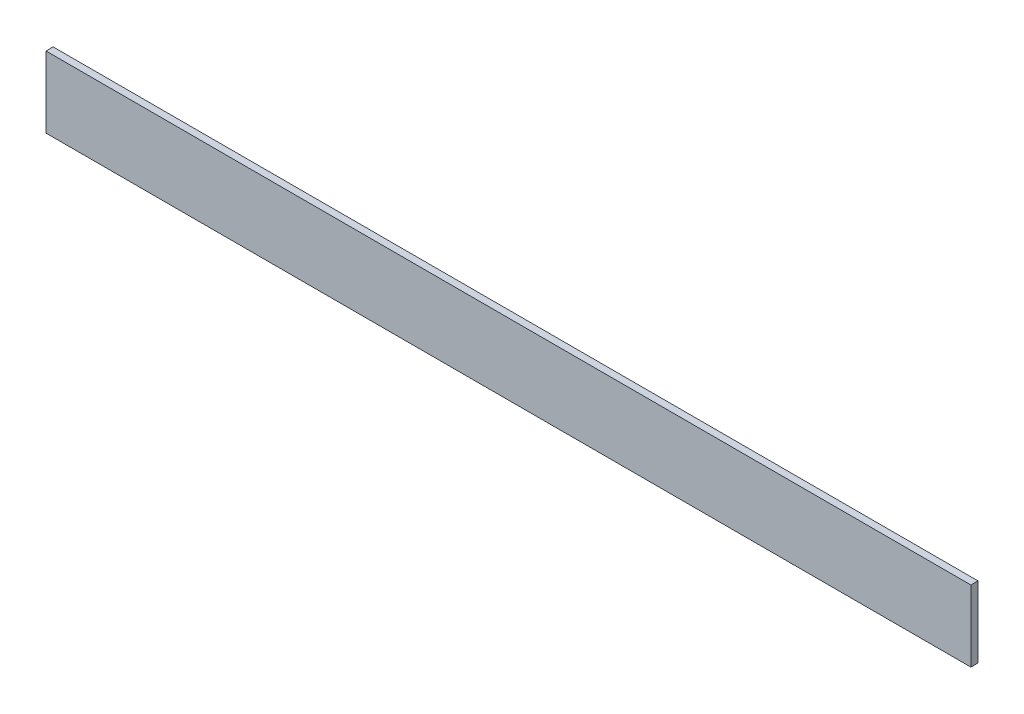
SolidWorks part; units mm, degrees
ref_plane "Ön Düzlem" through (0, 0, 0) normal (0, 0, 1) x (1, 0, 0)
ref_plane "Üst Düzlem" through (0, 0, 0) normal (0, 1, 0) x (1, 0, 0)
ref_plane "Sağ Düzlem" through (0, 0, 0) normal (1, 0, 0) x (0, 0, -1)
sketch "Çizim1" plane through (0, 0, 0) normal (0, 0, 1) x (1, 0, 0)
  line L1 (0, 0) -> (1300, 0)
  line L2 (0, 0) -> (0, -100)
  line L3 (0, -100) -> (1300, -100)
  line L4 (1300, 0) -> (1300, -100)
  dimension "D1" = 1300
  dimension "D2" = 100
base flange "Taban-Flanş1" sketch "Çizim1" thickness 10 reverse thickness direction no parameters "D1"=5
sketch "Büküm-Çizgileri1" [suppressed] plane through (0, 0, 0) normal (0, 1, 0) x (1, 0, 0)
sketch "Sınırlandırma-Kutusu1" [suppressed] plane through (0, 0, 0) normal (0, 1, 0) x (1, 0, 0)
sheet metal parameters "Sac-Levha1" thickness 10 parameters "D1"=5
flat pattern "Düz-Çoğaltma1" [suppressed]
sketch "Büküm-Çizgileri2" plane through (0, 0, 0) normal (0, 1, 0) x (1, 0, 0)
sketch3d "Sınırlandırma-Kutusu2" [suppressed]
  line L0 (0, -100, 0) -> (1300, -100, 0) construction
  line L1 (0, 0, 0) -> (1300, 0, 0) construction
  line L2 (0, -100, 0) -> (0, 0, 0) construction
  line L3 (1300, -100, 0) -> (1300, 0, 0) construction
